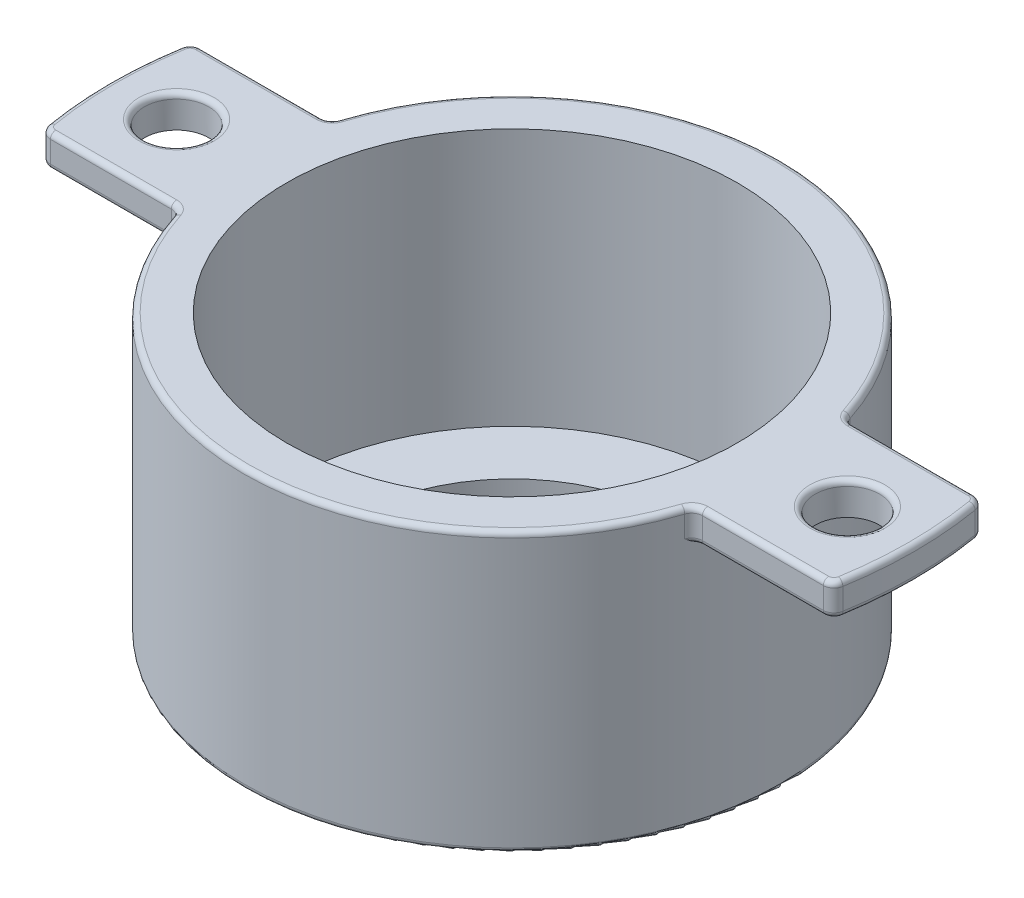
SolidWorks part; units mm, degrees
material "1060 合金"
ref_plane "Front Plane" through (0, 0, 0) normal (0, 0, 1) x (1, 0, 0)
ref_plane "Top Plane" through (0, 0, 0) normal (0, 1, 0) x (1, 0, 0)
ref_plane "Right Plane" through (0, 0, 0) normal (1, 0, 0) x (0, 0, -1)
sketch "Sketch4" plane through (0, 0, 0) normal (1, 0, 0) x (0, 0, -1)
  line L0 (0, 55) -> (0, -55) construction
  line L1 (-23.75, 26) -> (-25, 26)
  line L2 (-25, 26) -> (-25, 0)
  line L3 (55, 0) -> (-55, 0) construction
  line L4 (-25, 0) -> (-15, 0)
  line L5 (-15, 0) -> (-15, 2)
  line L6 (-15, 2) -> (-21, 2)
  line L7 (-21, 2) -> (-21, 26)
  line L8 (-21, 26) -> (-23.75, 26)
  line L13 (0, -1.1179) -> (0, 37.75) construction
  dimension "D1" = 2
  dimension "D3" = 26
  dimension "D5" = 21
  dimension "D6" = 4
  dimension "D7" = 10
revolve "Revolve1" add sketch "Sketch4" angle 360 about L13
sketch "Sketch5" plane through (0, 0, 0) normal (0, -1, 0) x (-1, 0, 0)
  line L0 (0, 22) -> (0, 0) construction
  line L1 (-5, 22) -> (5, 22)
  line L2 (-5, 22) -> (-5, 40)
  line L3 (-5, 40) -> (5, 40)
  line L4 (5, 22) -> (5, 40)
  circle A0 centre (0, 0) radius 15 construction
  dimension "D1" = 10
  dimension "D2" = 22
  dimension "D3" = 18
extrude "Boss-Extrude1" [suppressed] add sketch "Sketch5" against normal blind 37.75
sketch "Sketch6" [suppressed] plane through (-5, 0, 0) normal (-1, 0, 0) x (0, 0, 1)
  line L2 (-24.4949, 37.75) -> (-40, 37.75) construction
  line L3 (-40, 37.75) -> (-40, 0) construction
  circle A0 centre (-32.5, 28.95) radius 4
  circle A1 centre (-32.5, 8.95) radius 4
  dimension "D1" = 8
  dimension "D2" = 8
  dimension "D3" = 20
  dimension "D5" = 7.5
  dimension "D4" = 8.8
extrude "Cut-Extrude1" [suppressed] cut sketch "Sketch6" against normal blind 20
sketch "Sketch7" plane through (0, 26, 0) normal (0, 1, 0) x (1, 0, 0)
  line L0 (-36.8409, -7) -> (-24, -7)
  line L1 (36.8409, 7) -> (24, 7)
  line L2 (24, -7) -> (36.8409, -7)
  line L3 (-24, 7) -> (-36.8409, 7)
  arc A0 (-24, 7) -> (-24, -7) centre (0, 0) ccw
  arc A1 (36.8409, -7) -> (36.8409, 7) centre (0, 0) ccw
  circle A2 centre (0, 0) radius 21 construction
  circle A3 centre (0, 0) radius 21 construction
  arc A4 (-36.8409, 7) -> (-36.8409, -7) centre (0, 0) ccw
  arc A5 (24, -7) -> (24, 7) centre (0, 0) ccw
  dimension "D1" = 50
  dimension "D2" = 75
  dimension "D4" = 7
  dimension "D3" = 7
extrude "Boss-Extrude2" add sketch "Sketch7" against normal blind 3
sketch "Sketch8" plane through (0, 26, 0) normal (0, 1, 0) x (1, 0, 0)
  line L0 (-55, 0) -> (55, 0) construction
  line L2 (0, -14.3) -> (0, 14.3) construction
  circle A0 centre (31.25, 0) radius 3
  circle A2 centre (0, 0) radius 21 construction
  circle A7 centre (-31.25, 0) radius 3
  dimension "D1" = 6
  dimension "D4" = 31.25
extrude "Cut-Extrude2" cut sketch "Sketch8" against normal blind 7
fillet "圆角1" radius 1 8 edges at (-24, 24.5, 7) (-36.8409, 24.5, 7) (-36.8409, 24.5, -7) (-24, 24.5, -7) (24, 24.5, -7) (24, 24.5, 7) (36.8409, 24.5, 7) (36.8409, 24.5, -7)
fillet "圆角2" radius 0.5 16 edges at (24.1503, 26, 7.1914) (0, 26, 25) (-24.1503, 26, 7.1914) (-30.3711, 26, 7) (-36.6499, 26, 6.763) (-37.5, 26, 0) (-36.6499, 26, -6.763) (-30.3711, 26, -7) (-24.1503, 26, -7.1914) (0, 26, -25) (24.1503, 26, -7.1914) (30.3711, 26, -7) (36.6499, 26, -6.763) (37.5, 26, 0) (36.6499, 26, 6.763) (30.3711, 26, 7)
fillet "圆角3" radius 0.5 16 edges at (-24.1503, 23, -7.1914) (-24.1503, 23, 7.1914) (-30.3711, 23, 7) (-36.6499, 23, 6.763) (-37.5, 23, 0) (-36.6499, 23, -6.763) (24.1503, 23, 7.1914) (30.3711, 23, 7) (36.6499, 23, 6.763) (37.5, 23, 0) (36.6499, 23, -6.763) (24.1503, 23, -7.1914) (-31.25, 26, -3) (31.25, 26, 3) (-30.3711, 23, -7) (30.3711, 23, -7)
fillet "圆角4" radius 0.5 2 edges at (0, 0, -25) (0, 0, -15)
